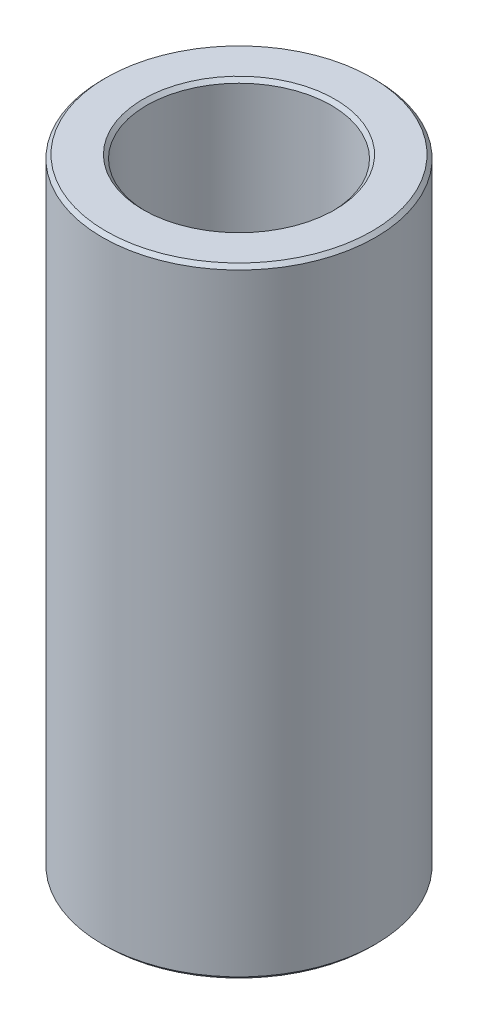
SolidWorks part; units mm, degrees
ref_plane "Front Plane" through (0, 0, 0) normal (0, 0, 1) x (1, 0, 0)
ref_plane "Top Plane" through (0, 0, 0) normal (0, 1, 0) x (1, 0, 0)
ref_plane "Right Plane" through (0, 0, 0) normal (1, 0, 0) x (0, 0, -1)
sketch "Sketch1" plane through (0, 0, 0) normal (0, 1, 0) x (1, 0, 0)
  circle A0 centre (0, 0) radius 25
  dimension "SLEEVE_OD" = 50
extrude "Boss-Extrude1" add sketch "Sketch1" along normal blind 113.3828
sketch "Sketch2" plane through (0, 0, 0) normal (0, 1, 0) x (1, 0, 0)
  circle A0 centre (0, 0) radius 16.8993
  dimension "BORE_D" = 33.7986
extrude "Cut-Extrude1" cut sketch "Sketch2" along normal through all
chamfer "Chamfer1" distance 0.6544 angle 45 4 edges at (0, 113.3828, 16.8993) (0, 0, 16.8993) (0, 0, 25) (0, 113.3828, 25)
